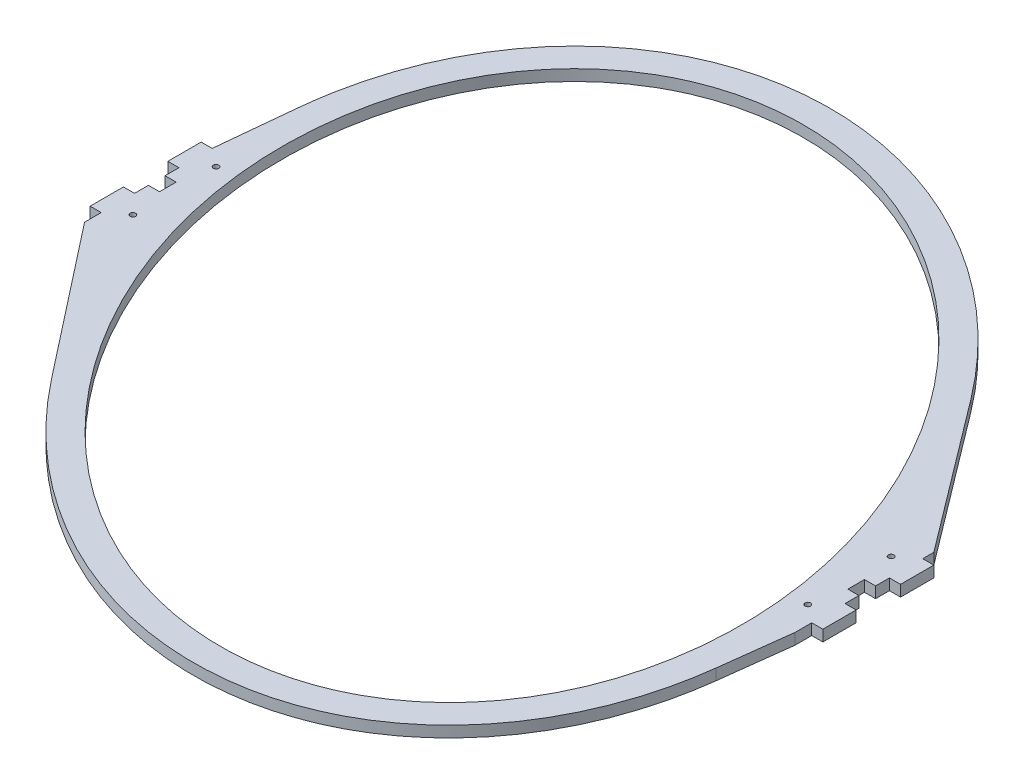
SolidWorks part; units mm, degrees
ref_plane "Front Plane" through (0, 0, 0) normal (0, 0, 1) x (1, 0, 0)
ref_plane "Top Plane" through (0, 0, 0) normal (0, 1, 0) x (1, 0, 0)
ref_plane "Right Plane" through (0, 0, 0) normal (1, 0, 0) x (0, 0, -1)
sketch "Sketch1" plane through (0, 0, 0) normal (0, 1, 0) x (1, 0, 0)
  line L0 (0, 520.2694) -> (0, -520.3963) construction
  line L1 (-478.2136, 0) -> (435.079, 0) construction
  line L2 (-270, 0) -> (-270, 60) construction
  line L3 (-270, 60) -> (-290, 60) construction
  line L4 (-290, 60) -> (-290, -60) construction
  line L5 (-320, 50) -> (-320, 51)
  line L6 (-330, -20) -> (-330, -50)
  line L7 (-320, -50) -> (-320, -65)
  line L8 (-330, -50) -> (-320, -50)
  line L9 (290, 60) -> (290, -60) construction
  line L10 (-320, -20) -> (-330, -20)
  line L11 (-320, 0) -> (-320, -20)
  line L12 (-320, 0) -> (-320, 20)
  line L13 (-320, 20) -> (-330, 20)
  line L14 (-330, 20) -> (-330, 50)
  line L15 (-330, 50) -> (-320, 50)
  line L16 (-320, 51) -> (-313.0913, 120.0927)
  line L17 (-320, -65) -> (-212.2821, -202.5885)
  line L19 (-290, 60) -> (-290, -60) construction
  line L29 (-177.5, 307.439) -> (177.5, -307.439) construction
  line L30 (320, 0) -> (320, 20)
  line L31 (320, 20) -> (330, 20)
  line L32 (330, 20) -> (330, 50)
  line L33 (330, 50) -> (320, 50)
  line L34 (320, 50) -> (320, 60)
  line L35 (320, 0) -> (320, -20)
  line L36 (320, -20) -> (330, -20)
  line L37 (330, -20) -> (330, -50)
  line L38 (330, -50) -> (320, -50)
  line L39 (320, -50) -> (320, -65)
  line L40 (320, -65) -> (312.1702, -128.3352)
  line L41 (320, 60) -> (217.5479, 195.7385)
  ellipse E0 centre (0, 0) end of major axis (-190, 329.0897) minor radius 290 (217.5479, 195.7385) -> (-313.0913, 120.0927) ccw
  ellipse E1 centre (0, 0) end of major axis (0, 380) minor radius 290 construction
  ellipse E3 centre (0, 0) end of major axis (-177.5, 307.439) minor radius 265
  ellipse E7 centre (0, 0) end of major axis (-190, 329.0897) minor radius 290 (-212.2821, -202.5885) -> (312.1702, -128.3352) ccw
  point P27 (290, 0)
  point P32 (-290, 0)
  point P42 (290, 0)
  dimension "D2" = 10
  dimension "D3" = 580
  dimension "D4" = 760
  dimension "D5" = 20
  dimension "D6" = 10
  dimension "D7" = 60
  dimension "D8" = 10
  dimension "D9" = 320
  dimension "D10" = 30
  dimension "D11" = 710
  dimension "D12" = 530
  dimension "D13" = 760
  dimension "D14" = 580
  dimension "D15" = 30
  dimension "D16" = 30
  dimension "D17" = 20
  dimension "D18" = 20
  dimension "D19" = 15
  dimension "D20" = 10
  dimension "D21" = 1
extrude "Boss-Extrude1" add sketch "Sketch1" along normal blind 10
sketch "Sketch2" plane through (0, 10, 0) normal (0, 1, 0) x (1, 0, 0)
  line L0 (0, 0) -> (451.8605, 0) construction
  line L1 (320, -20) -> (320, 20) construction
  line L2 (320, -7.5) -> (310, -7.5)
  line L3 (320, -7.5) -> (320, 7.5)
  line L4 (320, 7.5) -> (310, 7.5)
  line L5 (310, -7.5) -> (310, 7.5)
  line L6 (0, 0) -> (0, 314.2562) construction
  line L7 (-310, -7.5) -> (-310, 7.5)
  line L8 (-320, 7.5) -> (-310, 7.5)
  line L9 (-320, -7.5) -> (-320, 7.5)
  line L10 (-320, -7.5) -> (-310, -7.5)
  point P3 (-320, 0)
  point P10 (310, 0)
  point P11 (320, 0)
  point P13 (-310, 0)
  dimension "D1" = 15
  dimension "D2" = 10
extrude "Cut-Extrude1" cut sketch "Sketch2" against normal blind 10
hole_wizard "Ø5.0 (5) Diameter Hole2" positions "Sketch5" profile "Sketch6" hole size "Ø5.0" standard "ANSI Metric"
sketch "Sketch5" plane through (0, 10, 0) normal (0, 1, 0) x (1, 0, 0)
  point P0 (304, 37.5)
  point P3 (304, -37.5)
  point P6 (-304, -37.5)
  point P9 (-304, 37.5)
sketch "Sketch6" plane through (304, 10, -37.5) normal (1, 0, 0) x (0, 0, 1)
  line L0 (0, 0) -> (0, 26.5022)
  line L1 (0, 26.5022) -> (2.5, 25)
  line L2 (2.5, 25) -> (2.5, 0)
  line L3 (2.5, 0) -> (0, 0)
  line L4 (0, 26.5022) -> (-2.5, 25) construction
  line L5 (0, -6.35) -> (0, 107.95) construction
  dimension "Hole Dia." = 5
  dimension "Hole Depth" = 25
  dimension "Drill Angle" = 118
